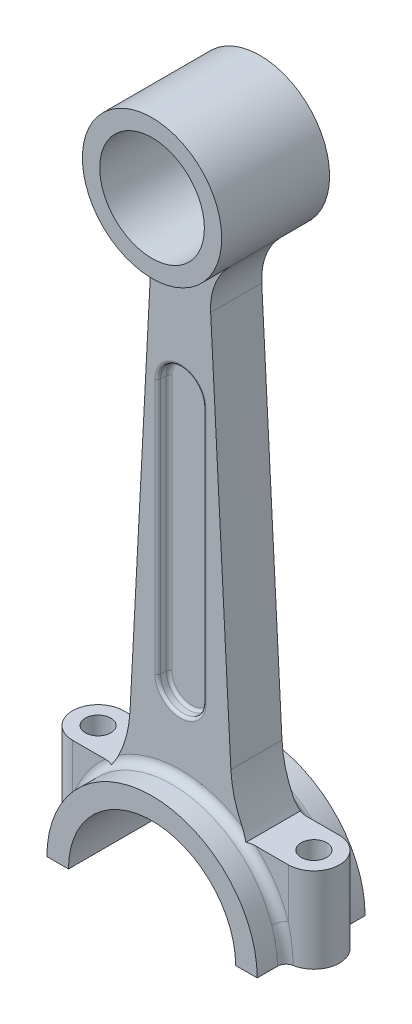
SolidWorks part; units mm, degrees
ref_plane "Front Plane" through (0, 0, 0) normal (0, 0, 1) x (1, 0, 0)
ref_plane "Top Plane" through (0, 0, 0) normal (0, 1, 0) x (1, 0, 0)
ref_plane "Right Plane" through (0, 0, 0) normal (1, 0, 0) x (0, 0, -1)
sketch "Sketch1" plane through (0, 0, 0) normal (0, 0, 1) x (1, 0, 0)
  line L0 (-18.645, -187.3564) -> (-10, -22.3996)
  line L1 (0, -219.3566) -> (0, 0) construction
  line L2 (18.645, -187.3564) -> (10, -22.3996)
  circle A0 centre (0, 0) radius 24.5304
  circle A1 centre (0, 0) radius 18.4251
  circle A2 centre (0, -219.3566) radius 37.0358
  circle A3 centre (0, -219.3566) radius 29.4365
  point P9 (0, 0)
  dimension "D1" = 20
  dimension "D2" = 6
extrude "Boss-Extrude2" add sketch "Sketch1" along normal mid plane 38 contours A0 A1 | A3 A2 region at (0, -183.3683, 0) region at (-12.9723, 19.9976, 0)
extrude "Boss-Extrude3" add sketch "Sketch1<5>" along normal mid plane 18 contours A2 L1 A0 L0 | L1 A2 L2 A0 region at (-7.4102, -111.7341, 0) region at (7.4102, -111.7341, 0)
sketch "Sketch1<5>" plane through (0, 0, 0) normal (0, 0, 1) x (1, 0, 0) same geometry as "Sketch1"
sketch "Sketch2" plane through (0, 0, 9) normal (0, 0, 1) x (1, 0, 0)
  line L0 (0, 0) -> (0, -219.3566) construction
  line L1 (0, -154.6783) -> (0, -64.6783) construction
  line L2 (-8, -154.6783) -> (-8, -64.6783)
  line L3 (8, -154.6783) -> (8, -64.6783)
  arc A0 (-8, -154.6783) -> (8, -154.6783) centre (0, -154.6783) ccw
  arc A1 (8, -64.6783) -> (-8, -64.6783) centre (0, -64.6783) ccw
  point P6 (0, -109.6783)
  dimension "D2" = 8
  dimension "D1" = 45
extrude "Cut-Extrude1" cut sketch "Sketch2" against normal blind 4
ref_plane "Plane1" through (0, 0, 0) normal (0, 0, 1) x (1, 0, 0)
mirror "Mirror1" about plane through (0, 0, 0) normal (0, 0, 1) of "Cut-Extrude1"
fillet "Fillet2" radius 1 16 edges at (8, -109.6783, 9) (0, -162.6783, 9) (-8, -109.6783, 9) (0, -162.6783, 5) (-8, -109.6783, 5) (0, -56.6783, 5) (0, -162.6783, -9) (-8, -109.6783, -9) (0, -56.6783, -9) (8, -109.6783, -5) (0, -56.6783, -5) (-8, -109.6783, -5) (0, -162.6783, -5) (0, -56.6783, 9) (8, -109.6783, 5) (8, -109.6783, -9)
sketch "Sketch3" plane through (0, 0, -19) normal (0, 0, -1) x (-1, 0, 0)
  line L0 (0, -219.3566) -> (37.0358, -219.3566)
  line L1 (37.0358, -219.3566) -> (0, -219.3566)
  line L2 (-37.0358, -219.3566) -> (0, -219.3566)
  circle A0 centre (0, -219.3566) radius 37.0358 construction
  arc A1 (37.0358, -219.3566) -> (-37.0358, -219.3566) centre (0, -219.3566) cw
  circle M1 centre (0, -219.3566) radius 37.0358
  circle M2 centre (0, -219.3566) radius 29.4365
extrude "Cut-Extrude2" cut sketch "Sketch3" against normal through all contours L2 L0 M1 M2 region at (-33.2362, -220.1848, -19)
fillet "Fillet3" radius 40 2 edges at (18.645, -187.3564, 0) (-18.645, -187.3564, 0)
fillet "Fillet4" radius 22.5 2 edges at (-10, -22.3996, 0) (10, -22.3996, 0)
ref_plane "Plane3" through (0, -189.3566, 0) normal (0, -1, 0) x (-1, 0, 0)
sketch "Sketch4" plane through (0, -189.3566, 0) normal (0, -1, 0) x (-1, 0, 0)
  line L0 (-38, 0) -> (38, 0) construction
  line L1 (-26.9835, 0) -> (26.9835, 0) construction
  line L2 (-38, 9) -> (38, 9)
  line L3 (-38, -9) -> (38, -9)
  arc A0 (-38, 9) -> (-38, -9) centre (-38, 0) ccw
  arc A1 (38, -9) -> (38, 9) centre (38, 0) ccw
  point P5 (0, 0)
  dimension "D2" = 9
  dimension "D1" = 76
extrude "Boss-Extrude6" add sketch "Sketch4" along normal through all contours A1 L2 A0 L3
sketch "Sketch7" plane through (0, 0, -9) normal (0, 0, -1) x (-1, 0, 0)
  line L1 (-29.4365, -219.3566) -> (29.4365, -219.3566)
  line L2 (-29.4365, -219.3566) -> (29.4365, -219.3566)
  arc A1 (29.4365, -219.3566) -> (-29.4365, -219.3566) centre (0, -219.3566) ccw
  arc A2 (29.4365, -219.3566) -> (-29.4365, -219.3566) centre (0, -219.3566) ccw
  dimension "D1" = 0
extrude "Cut-Extrude3" cut sketch "Sketch7" against normal through all
sketch "Sketch8" plane through (0, -189.3566, 0) normal (0, -1, 0) x (-1, 0, 0)
  circle A0 centre (38, 0) radius 4.5
extrude "Cut-Extrude4" cut sketch "Sketch8" along normal through all contours A0
mirror "Mirror2" about plane through (0, 0, 0) normal (1, 0, 0) of "Cut-Extrude4"
fillet "Fillet5" radius 3 2 edges at (0, -182.3208, -9) (0, -182.3208, 9)
